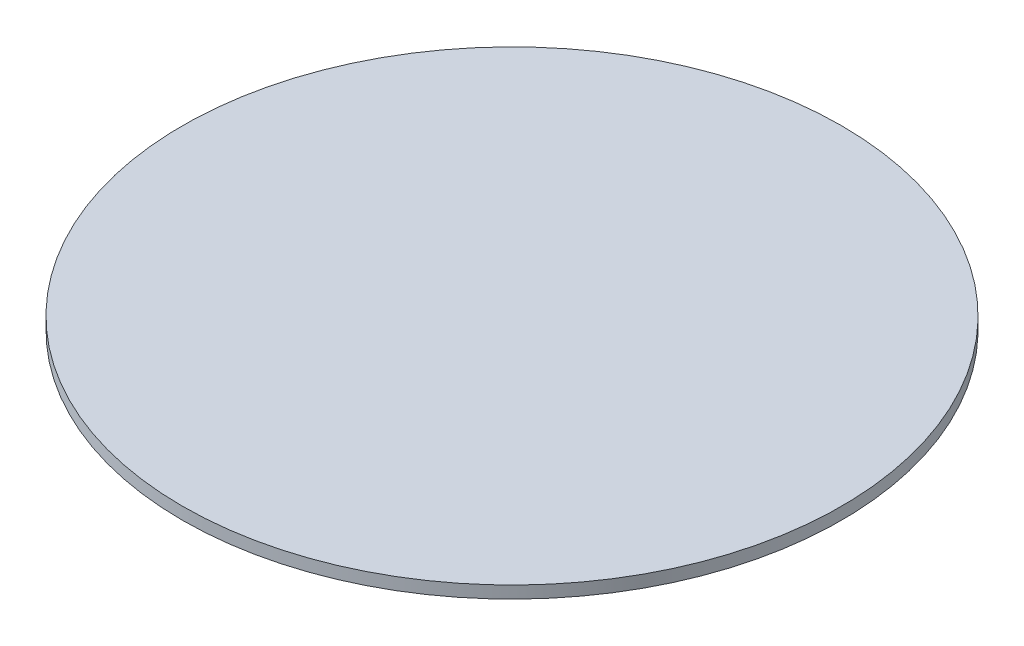
SolidWorks part; units mm, degrees
material "Brass"
ref_plane "Front Plane" through (0, 0, 0) normal (0, 0, 1) x (1, 0, 0)
ref_plane "Top Plane" through (0, 0, 0) normal (0, 1, 0) x (1, 0, 0)
ref_plane "Right Plane" through (0, 0, 0) normal (1, 0, 0) x (0, 0, -1)
sketch "Sketch2" plane through (0, 0, 0) normal (0, 1, 0) x (1, 0, 0)
  circle A0 centre (0, 0) radius 13.5
  dimension "D1" = 27
extrude "Boss-Extrude1" add sketch "Sketch2" along normal blind 0.5
